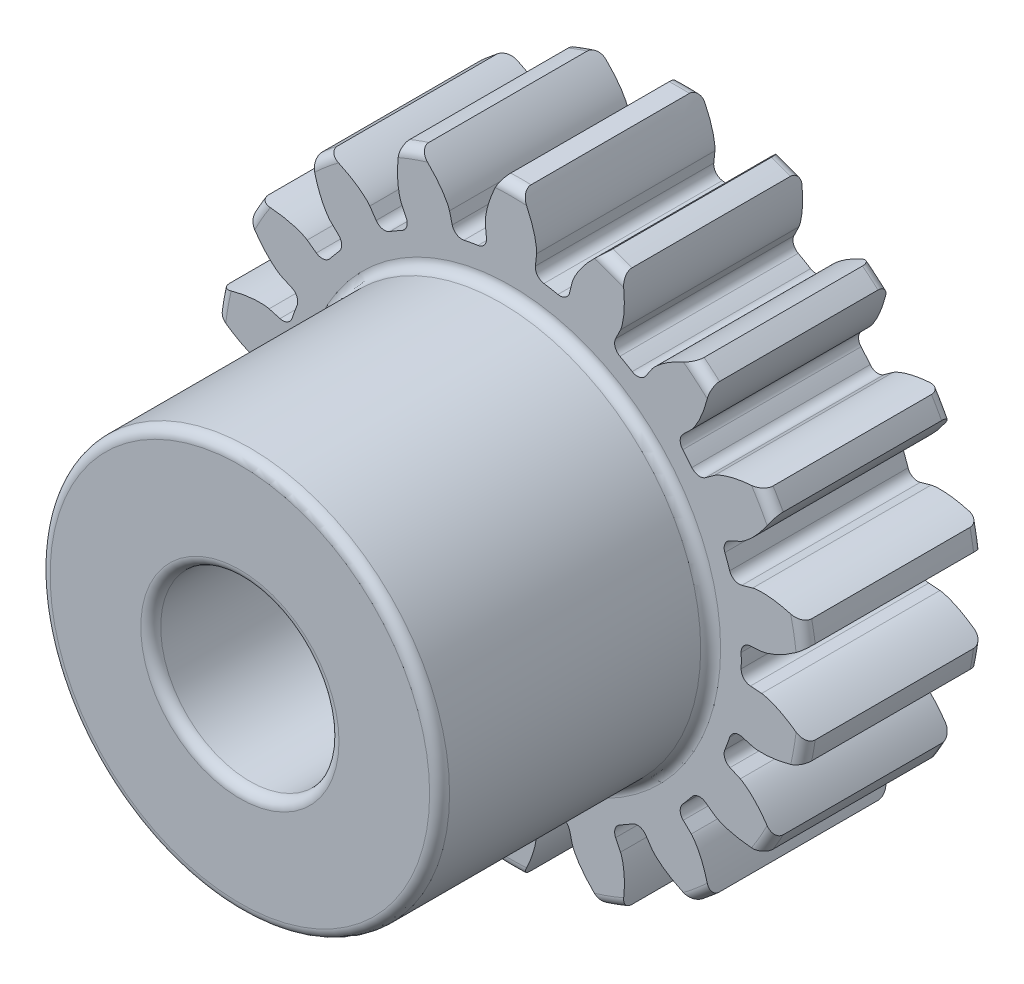
SolidWorks part; units mm, degrees
ref_plane "Front Plane" through (0, 0, 0) normal (0, 0, 1) x (1, 0, 0)
ref_plane "Top Plane" through (0, 0, 0) normal (0, 1, 0) x (1, 0, 0)
ref_plane "Right Plane" through (0, 0, 0) normal (1, 0, 0) x (0, 0, -1)
sketch "Sketch1" plane through (0, 0, 0) normal (0, 0, 1) x (1, 0, 0)
  line L0 (0, 0) -> (0, 4.7625) construction
  line L1 (-1.5306, 5.3196) -> (1.5306, 4.2054) construction
  circle A0 centre (0, 0) radius 4.101 construction
  circle A1 centre (0, 0) radius 5.2917 construction
  circle A2 centre (0, 0) radius 4.7625 construction
  circle A3 centre (0, 0) radius 4.4753 construction
  circle A4 centre (0, 0) radius 1.5875 construction
  circle A5 centre (0, 0) radius 3.556 construction
  point P8 (609.6, 0)
  point P13 (228.6, 0)
  dimension "OD | Outside Diameter" = 10.5833
  dimension "Root Diameter" = 8.2021
  dimension "Gear Pitch Diameter" = 9.525
  dimension "Base Diameter" = 8.9506
  dimension "For Shaft Diameter" = 3.175
  dimension "Hub Diameter" = 7.112
  dimension "Pressure Angle" = 20
  dimension "Number of Teeth" = 457.2
  dimension "Gear Pitch | Diametral Pitch" = 1219.2
sketch "Sketch2" plane through (0, 0, 0) normal (1, 0, 0) x (0, 0, -1)
  line L0 (-4.0005, 0) -> (4.0005, 0) construction
  line L1 (-4.0005, 5.2917) -> (4.0005, 5.2917) construction
  point P2 (0, 5.2917)
  point P4 (0.8255, 0)
  point P6 (0.8255, 5.2917)
  dimension "Overall Width" = 8.001
  dimension "Hub Width" = 4.826
  dimension "Face Width" = 3.175
sketch "Sketch3" plane through (0, 0, 0) normal (0, 0, 1) x (1, 0, 0)
  circle A0 centre (0, 0) radius 5.2917
  circle A1 centre (0, 0) radius 5.2917 construction
extrude "Boss-Extrude1" add sketch "Sketch3" against normal up to vertex (4.0005 mm away) and the other way up to vertex (4.0005 mm away) up to point (0, 0, -4.0005) other way up to point (0, 0, 4.0005)
sketch "Sketch5" plane through (0, 0, 0) normal (1, 0, 0) x (0, 0, -1)
  line L1 (-4.0005, 5.2917) -> (0.8255, 5.2917)
  line L2 (-4.0005, 5.2917) -> (-4.0005, 3.556)
  line L3 (-4.0005, 3.556) -> (0.8255, 3.556)
  line L4 (0.8255, 5.2917) -> (0.8255, 3.556)
  line L11 (4.0005, 1.5875) -> (-4.0005, 1.5875)
  line L12 (4.0005, 1.5875) -> (4.0005, 0)
  line L13 (4.0005, 0) -> (-4.0005, 0)
  line L14 (-4.0005, 1.5875) -> (-4.0005, 0)
  point P5 (0, 1.5875)
  point P12 (0, 3.556)
revolve "Cut-Revolve1" cut sketch "Sketch5" angle 360 about L0
fillet "Fillet2" radius 0.1775 6 edges at (5.2917, 0, -4.0005) (1.5875, 0, -4.0005) (1.5875, 0, 4.0005) (3.556, 0, -0.8255) (5.2917, 0, -0.8255) (3.556, 0, 4.0005)
sketch "Sketch4" plane through (0, 0, 0) normal (0, 0, 1) x (1, 0, 0)
  line L0 (0, 0) -> (4.0903, 0.2965) construction
  line L2 (0, 0) -> (4.0903, -0.2965) construction
  line L4 (4.0903, 0.2965) -> (4.4636, 0.3236)
  line L5 (4.4636, -0.3236) -> (4.0903, -0.2965)
  arc A0 (4.0903, 0.2965) -> (4.0903, -0.2965) centre (0, 0) cw
  arc A3 (5.2396, 0.7408) -> (5.2396, -0.7408) centre (0, 0) cw
  circle A4 centre (0, 0) radius 5.2917 construction
  spline S0 degree 4 poles (4.4636, 0.3236) (4.4649, 0.3237) (4.4686, 0.324) (4.4755, 0.325) (4.4868, 0.3268) (4.5011, 0.3295) (4.5195, 0.3335) (4.5411, 0.339) (4.5648, 0.3456) (4.5904, 0.3536) (4.6158, 0.3621) (4.641, 0.3713) (4.666, 0.381) (4.6961, 0.3934) (4.732, 0.4091) (4.7737, 0.4287) (4.8205, 0.4525) (4.8677, 0.4784) (4.9138, 0.5051) (4.9599, 0.5336) (5.0042, 0.5623) (5.0496, 0.5936) (5.0913, 0.6232) (5.1373, 0.6581) (5.1743, 0.6867) (5.2224, 0.7262) (5.2506, 0.75) (5.2834, 0.7786) (5.2978, 0.7915) (5.3067, 0.7995) knots 0 0 0 0 0 0.005377 0.015084 0.028532 0.04661 0.064855 0.092111 0.119476 0.146842 0.174209 0.201575 0.228941 0.256307 0.307035 0.361767 0.4165 0.471232 0.525964 0.580697 0.635429 0.690161 0.744894 0.799626 0.854358 0.909091 0.954545 1 1 1 1 1 construction
  spline S1 degree 4 poles (4.4636, 0.3236) (4.4649, 0.3237) (4.4686, 0.324) (4.4755, 0.325) (4.4868, 0.3268) (4.5011, 0.3295) (4.5195, 0.3335) (4.5411, 0.339) (4.5648, 0.3456) (4.5904, 0.3536) (4.6158, 0.3621) (4.641, 0.3713) (4.666, 0.381) (4.6961, 0.3934) (4.732, 0.4091) (4.7737, 0.4287) (4.8205, 0.4525) (4.8677, 0.4784) (4.9138, 0.5051) (4.9599, 0.5336) (5.0042, 0.5623) (5.0496, 0.5936) (5.0913, 0.6232) (5.1373, 0.6581) (5.1743, 0.6867) (5.212, 0.7176) (5.2303, 0.7329) (5.2396, 0.7408) knots 0 0 0 0 0 0.005377 0.015084 0.028532 0.04661 0.064855 0.092111 0.119476 0.146842 0.174209 0.201575 0.228941 0.256307 0.307035 0.361767 0.4165 0.471232 0.525964 0.580697 0.635429 0.690161 0.744894 0.799626 0.854358 0.909091 0.909091 0.909091 0.909091 0.909091
  spline S2 degree 4 poles (4.4636, -0.3236) (4.4649, -0.3237) (4.4686, -0.324) (4.4755, -0.325) (4.4868, -0.3268) (4.5011, -0.3295) (4.5195, -0.3335) (4.5411, -0.339) (4.5648, -0.3456) (4.5904, -0.3536) (4.6158, -0.3621) (4.641, -0.3713) (4.666, -0.381) (4.6961, -0.3934) (4.732, -0.4091) (4.7737, -0.4287) (4.8205, -0.4525) (4.8677, -0.4784) (4.9138, -0.5051) (4.9599, -0.5336) (5.0042, -0.5623) (5.0496, -0.5936) (5.0913, -0.6232) (5.1373, -0.6581) (5.1743, -0.6867) (5.2224, -0.7262) (5.2506, -0.75) (5.2834, -0.7786) (5.2978, -0.7915) (5.3067, -0.7995) knots 0 0 0 0 0 0.005377 0.015084 0.028532 0.04661 0.064855 0.092111 0.119476 0.146842 0.174209 0.201575 0.228941 0.256307 0.307035 0.361767 0.4165 0.471232 0.525964 0.580697 0.635429 0.690161 0.744894 0.799626 0.854358 0.909091 0.954545 1 1 1 1 1 construction
  spline S3 degree 4 poles (4.4636, -0.3236) (4.4649, -0.3237) (4.4686, -0.324) (4.4755, -0.325) (4.4868, -0.3268) (4.5011, -0.3295) (4.5195, -0.3335) (4.5411, -0.339) (4.5648, -0.3456) (4.5904, -0.3536) (4.6158, -0.3621) (4.641, -0.3713) (4.666, -0.381) (4.6961, -0.3934) (4.732, -0.4091) (4.7737, -0.4287) (4.8205, -0.4525) (4.8677, -0.4784) (4.9138, -0.5051) (4.9599, -0.5336) (5.0042, -0.5623) (5.0496, -0.5936) (5.0913, -0.6232) (5.1373, -0.6581) (5.1743, -0.6867) (5.212, -0.7176) (5.2303, -0.7329) (5.2396, -0.7408) knots 0 0 0 0 0 0.005377 0.015084 0.028532 0.04661 0.064855 0.092111 0.119476 0.146842 0.174209 0.201575 0.228941 0.256307 0.307035 0.361767 0.4165 0.471232 0.525964 0.580697 0.635429 0.690161 0.744894 0.799626 0.854358 0.909091 0.909091 0.909091 0.909091 0.909091
  dimension "D1" = 8.2021
extrude "Cut-Extrude1" cut sketch "Sketch4" against normal through all both and the other way through all
fillet "Fillet1" radius 0.1775 2 edges at (4.0903, -0.2965, -2.413) (4.0903, 0.2965, -2.413)
pattern_circular "CirPattern1" count 18 over 360 about axis through (0, 0, 4.0005) along (0, 0, -1) of "Cut-Extrude1", "Fillet1"
equation "\"Root Diameter@Sketch1\"=\"Root Diameter\""
equation "\"OD | Outside Diameter@Sketch1\"=\"Outside Diameter\""
equation "\"D1@CirPattern1\"=\"Number of Teeth\""
equation "\"Diametral Pitch\"= 48"
equation "\"Number of Teeth\"= 18"
equation "\"Pressure Angle\"=20"
equation "\"Pitch Diameter\"= \"Number of Teeth\" / \"Diametral Pitch\""
equation "\"Base Diameter\"= \"Pitch Diameter\" * cos ( \"Pressure Angle\" )"
equation "\"Outside Diameter\"= ( \"Number of Teeth\" + 2 ) / \"Diametral Pitch\""
equation "\"Dedendum\"= 1.25 / \"Diametral Pitch\""
equation "\"Root Diameter\"= \"Pitch Diameter\" - ( 2 * \"Dedendum\" )"
equation "\"Pitch Angle\"= 360deg / \"Number of Teeth\""
equation "\"Alpha\"= sqr ( \"Pitch Diameter\" ^ 2 - \"Base Diameter\" ^ 2 ) / \"Base Diameter\" * 180 / PI - \"Pressure Angle\""
equation "\"Beta\"= ( \"Pitch Angle\" / 4 - \"Alpha\" )"
equation "\"Phi\"= sqr ( ( \"Outside Diameter\" / 2 ) ^ 2 - ( \"Base Diameter\" / 2 ) ^ 2 ) / ( \"Base Diameter\" / 2 )"
equation "\"Addendum\"= 1 / \"Diametral Pitch\""
equation "\"WorkingDepth\"= 2 / \"Diametral Pitch\""
equation "\"WholeDepth\"= 2.25 / \"Diametral Pitch\""
equation "\"Clearance\"= 0.25 / \"Diametral Pitch\""
equation "\"ToothThickness\"= ( pi * 2 ) / \"Diametral Pitch\""
equation "\"CircularPitch\"= pi / \"Diametral Pitch\""
equation "\"Number of Teeth@Sketch1\"=\"Number of Teeth\""
equation "\"Gear Pitch | Diametral Pitch@Sketch1\"=\"Diametral Pitch\""
equation "\"Pressure Angle@Sketch1\"=\"Pressure Angle\""
equation "\"Gear Pitch Diameter@Sketch1\"=\"Pitch Diameter\""
equation "\"Base Diameter@Sketch1\"=\"Base Diameter\""
equation "\"Fillet\"= \"Clearance\" * cos ( \"Pressure Angle\" ) * tan ( ( 90 + \"Pressure Angle\" ) / 2 )"
equation "\"D1@Fillet1\"=\"Fillet\""
equation "\"D1@Sketch4\"=if( \"Base Diameter\">\"Root Diameter\",\"Root Diameter\",\"Base Diameter\"-.00001)"
equation "\"D1@Fillet2\"=\"Fillet\""
